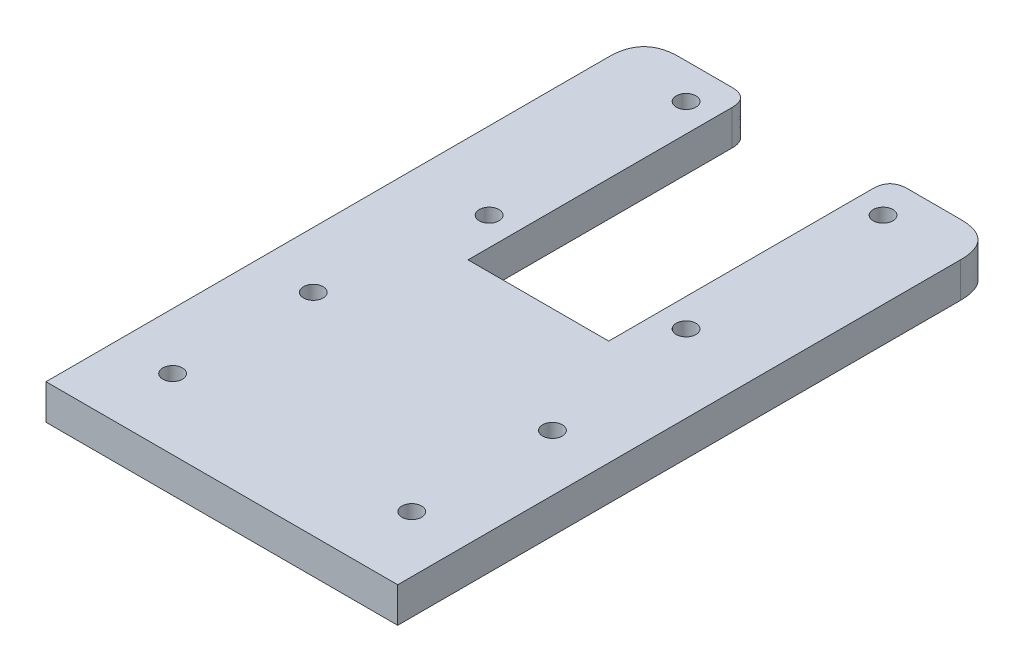
SolidWorks part; units mm, degrees
ref_plane "Front Plane" through (0, 0, 0) normal (0, 0, 1) x (1, 0, 0)
ref_plane "Top Plane" through (0, 0, 0) normal (0, 1, 0) x (1, 0, 0)
ref_plane "Right Plane" through (0, 0, 0) normal (1, 0, 0) x (0, 0, -1)
sketch "Sketch1" plane through (0, 0, 0) normal (0, 1, 0) x (1, 0, 0)
  line L1 (25, -42.5) -> (-25, -42.5)
  line L2 (25, -42.5) -> (25, 42.5)
  line L3 (25, 42.5) -> (-25, 42.5)
  line L4 (-25, -42.5) -> (-25, 42.5)
  line L5 (25, -42.5) -> (-25, 42.5) construction
  line L6 (25, 42.5) -> (-25, -42.5) construction
  point P0 (0, 0)
  dimension "D1" = 50
  dimension "D2" = 85
extrude "Boss-Extrude1" add sketch "Sketch1" along normal blind 5
sketch "Sketch2" plane through (0, 5, 0) normal (0, 1, 0) x (1, 0, 0)
  line L0 (25, 42.5) -> (-25, 42.5) construction
  line L2 (-25, 42.5) -> (-25, -42.5) construction
  line L4 (25, -42.5) -> (25, 42.5) construction
  circle A0 centre (-14, 37.5) radius 1.4
  circle A1 centre (14, 37.5) radius 1.4
  circle A2 centre (-14, 9.5) radius 1.4
  circle A3 centre (14, 9.5) radius 1.4
  dimension "D1" = 5
  dimension "D6" = 11
  dimension "D2" = 5
  dimension "D3" = 28
  dimension "D4" = 28
  dimension "D5" = 28
  dimension "D7" = 11
  dimension "D8" = 28
  dimension "D9" = 11
extrude "Cut-Extrude1" cut sketch "Sketch2" against normal blind 5
sketch "Sketch3" plane through (0, 5, 0) normal (0, 1, 0) x (1, 0, 0)
  line L0 (25, 42.5) -> (-25, 42.5) construction
  line L1 (10, 2.5) -> (-10, 2.5)
  line L2 (10, 2.5) -> (10, 42.5)
  line L3 (10, 42.5) -> (-10, 42.5)
  line L4 (-10, 2.5) -> (-10, 42.5)
  line L5 (10, 2.5) -> (-10, 42.5) construction
  line L6 (10, 42.5) -> (-10, 2.5) construction
  point P0 (0, 22.5)
  dimension "D1" = 40
  dimension "D2" = 20
  dimension "D3" = 0
extrude "Cut-Extrude2" cut sketch "Sketch3" against normal blind 5
fillet "Fillet3" radius 5 1 edges at (-25, 2.5, -42.5) conic rho 0.5
fillet "Fillet4" radius 5 1 edges at (25, 2.5, -42.5) conic rho 0.5
fillet "Fillet5" radius 2.5 1 edges at (-10, 2.5, -42.5) conic rho 0.5
fillet "Fillet6" radius 2.5 1 edges at (10, 2.5, -42.5) conic rho 0.5
sketch "Sketch4" plane through (0, 5, 0) normal (0, 1, 0) x (1, 0, 0)
  line L1 (-25, -42.5) -> (25, -42.5) construction
  line L2 (-25, 37.5) -> (-25, -42.5) construction
  circle A0 centre (-17, -32.5) radius 1.4
  circle A1 centre (17, -32.5) radius 1.4
  circle A2 centre (17, -12.5) radius 1.4
  circle A3 centre (-17, -12.5) radius 1.4
  dimension "D1" = 8
  dimension "D4" = 20
  dimension "D2" = 10
  dimension "D3" = 10
extrude "Cut-Extrude3" cut sketch "Sketch4" against normal blind 5
